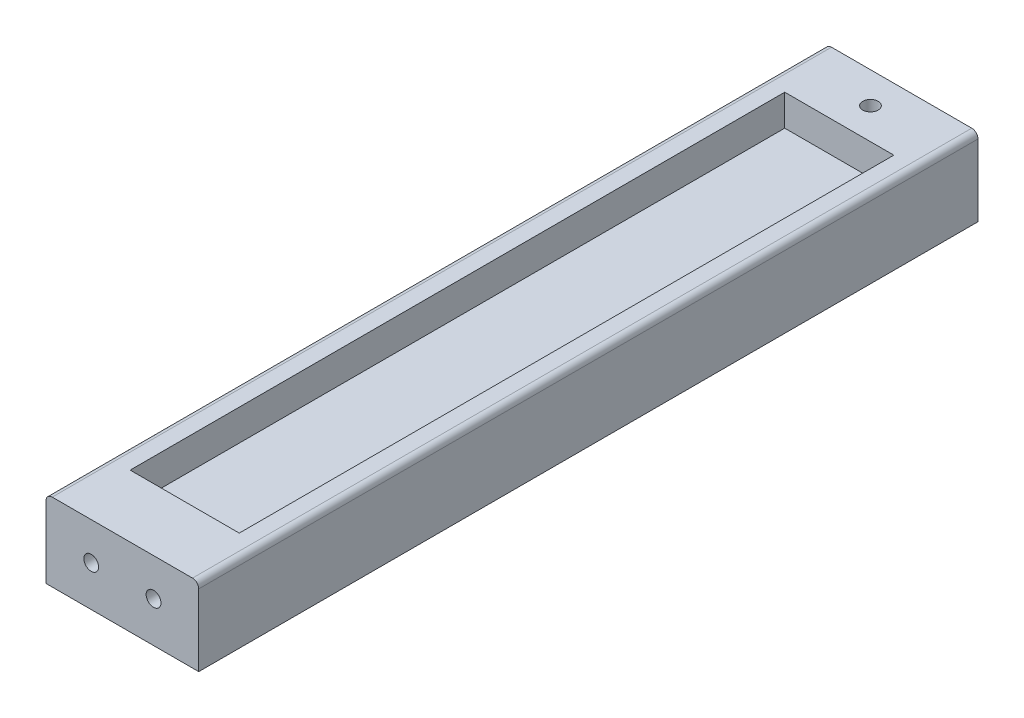
SolidWorks part; units mm, degrees
ref_plane "Front Plane" through (0, 0, 0) normal (0, 0, 1) x (1, 0, 0)
ref_plane "Top Plane" through (0, 0, 0) normal (0, 1, 0) x (1, 0, 0)
ref_plane "Right Plane" through (0, 0, 0) normal (1, 0, 0) x (0, 0, -1)
sketch "Sketch1" plane through (0, 0, 0) normal (0, 0, 1) x (1, 0, 0)
  line L1 (24.5, -10) -> (-24.5, -10)
  line L2 (24.5, -10) -> (24.5, 10)
  line L3 (24.5, 10) -> (-24.5, 10)
  line L4 (-24.5, -10) -> (-24.5, 10)
  line L5 (0, 10) -> (0, -10) construction
  line L6 (24.5, 0) -> (-24.5, 0) construction
  point P0 (0, 0)
  dimension "D1" = 20
  dimension "D2" = 49
extrude "Boss-Extrude1" add sketch "Sketch1" along normal mid plane 250
sketch "Sketch3" plane through (0, 10, 0) normal (0, 1, 0) x (1, 0, 0)
  line L0 (24.5, 125) -> (-24.5, 125) construction
  line L1 (24.5, 125) -> (-24.5, 125)
  line L2 (24.5, 125) -> (24.5, -125)
  line L3 (24.5, -125) -> (-24.5, -125)
  line L4 (-24.5, 125) -> (-24.5, -125)
  line L5 (0, -125) -> (0, 125) construction
  line L6 (24.5, 0) -> (-24.5, 0) construction
  point P0 (0, 0)
  dimension "D1" = 49
extrude "Boss-Extrude2" add sketch "Sketch3" along normal blind 5
ref_plane "Plane1" through (0, 15, 0) normal (0, 1, 0) x (1, 0, 0)
sketch "Sketch2" plane through (0, 15, 0) normal (0, 1, 0) x (1, 0, 0)
  line L1 (24.5, 125) -> (-24.5, 125) construction
  circle A0 centre (0, 115) radius 2.46
  dimension "D1" = 4.92
  dimension "D2" = 10
extrude "Cut-Extrude1" cut sketch "Sketch2" against normal blind 10 and the other way through all
sketch "Sketch5" plane through (0, 15, 0) normal (0, 1, 0) x (1, 0, 0)
  line L1 (-17.5, -105) -> (17.5, -105)
  line L2 (-17.5, -105) -> (-17.5, 105)
  line L3 (-17.5, 105) -> (17.5, 105)
  line L4 (17.5, -105) -> (17.5, 105)
  line L5 (-17.5, -105) -> (17.5, 105) construction
  line L6 (-17.5, 105) -> (17.5, -105) construction
  point P0 (0, 0)
  dimension "D1" = 35
  dimension "D2" = 210
extrude "Cut-Extrude3" cut sketch "Sketch5" against normal blind 10
fillet "Fillet1" radius 2 2 edges at (-24.5, 15, 0) (24.5, 15, 0)
sketch "Sketch4" plane through (0, -10, 0) normal (0, -1, 0) x (1, 0, 0)
  line L0 (-24.5, 125) -> (24.5, 125) construction
  line L5 (24.5, 125) -> (24.5, -125) construction
  circle A0 centre (-0.5, 110) radius 7.874
  dimension "D2" = 15.748
  dimension "D1" = 15
  dimension "D3" = 25
extrude "Cut-Extrude2" cut sketch "Sketch4" against normal blind 10
sketch "Sketch6" plane through (0, 0, 125) normal (0, 0, 1) x (1, 0, 0)
  circle A0 centre (10, 3) radius 2.375
  circle A1 centre (-10, 3) radius 2.375
  point P4 (0, 0)
  dimension "D1" = 4.75
  dimension "D2" = 4.75
  dimension "D3" = 10
  dimension "D4" = 3
  dimension "D5" = 10
  dimension "D6" = 3
extrude "Cut-Extrude4" cut sketch "Sketch6" against normal blind 10
